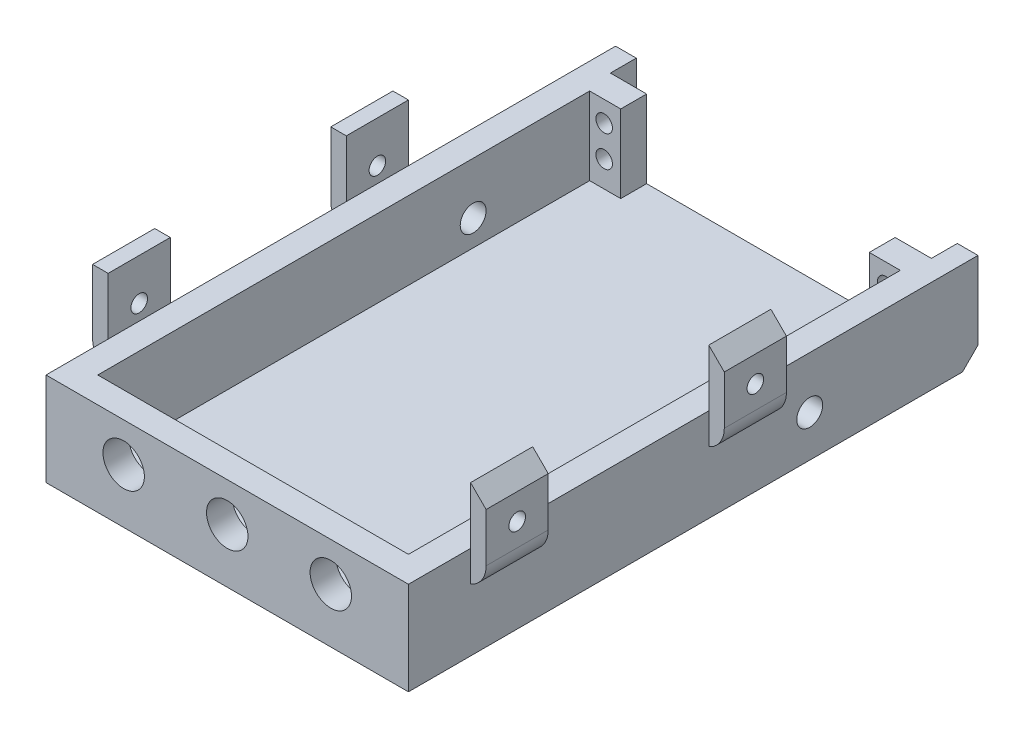
SolidWorks part; units mm, degrees
ref_plane "Alzado" through (0, 0, 0) normal (0, 0, 1) x (1, 0, 0)
ref_plane "Planta" through (0, 0, 0) normal (0, 1, 0) x (1, 0, 0)
ref_plane "Vista lateral" through (0, 0, 0) normal (1, 0, 0) x (0, 0, -1)
sketch "Croquis1" plane through (0, 0, 0) normal (0, 1, 0) x (1, 0, 0)
  line L1 (-35, 52.5) -> (35, 52.5)
  line L2 (-35, 52.5) -> (-35, -52.5)
  line L3 (-35, -52.5) -> (35, -52.5)
  line L4 (35, 52.5) -> (35, -52.5)
  line L5 (-35, 52.5) -> (35, -52.5) construction
  line L6 (-35, -52.5) -> (35, 52.5) construction
  point P0 (0, 0)
  dimension "D1" = 105
  dimension "D2" = 70
extrude "Saliente-Extruir1" add sketch "Croquis1" along normal blind 3
sketch "Croquis2" plane through (0, 3, 0) normal (0, 1, 0) x (1, 0, 0)
  line L1 (-35, 52.5) -> (-30, 52.5)
  line L2 (-35, 52.5) -> (-35, -52.5)
  line L4 (-30, 52.5) -> (-30, -47.5)
  line L5 (35, 52.5) -> (-35, 52.5) construction
  line L7 (35, -52.5) -> (35, 52.5)
  line L8 (35, 52.5) -> (30, 52.5)
  line L9 (30, -47.5) -> (30, 52.5)
  line L10 (-35, -52.5) -> (35, -52.5)
  line L12 (-30, -47.5) -> (30, -47.5)
  dimension "D1" = 5
  dimension "D2" = 5
  dimension "D3" = 100
  dimension "D4" = 100
extrude "Saliente-Extruir2" add sketch "Croquis2" along normal blind 15
ref_plane "Plano1" through (0, 0, -46.5) normal (0, 0, -1) x (-1, 0, 0)
sketch "Croquis10" plane through (35, 0, 0) normal (1, 0, 0) x (0, 0, -1)
  line L0 (11.5, 29) -> (11.5, 12) construction
  line L5 (-31.5, 18) -> (8.5, 18) construction
  line L10 (55, 0) -> (-55, 0) construction
  line L15 (8.5, 12) -> (17.5, 12)
  line L16 (8.5, 12) -> (8.5, 29)
  line L17 (8.5, 29) -> (17.5, 29)
  line L18 (17.5, 12) -> (17.5, 29)
  line L19 (-34.5, 12) -> (-28.5, 12)
  line L20 (11.5, 12) -> (5.5, 12)
  line L22 (11.5, 29) -> (5.5, 29)
  line L23 (5.5, 12) -> (5.5, 29)
  line L24 (-31.5, 12) -> (-40.5, 12)
  line L25 (-11.5, 11.4546) -> (-11.5, 24.5454)
  line L26 (52.5, 18) -> (52.5, 0) construction
  line L27 (-52.5, 18) -> (-52.5, 0) construction
  line L28 (-52.5, 0) -> (52.5, 0) construction
  line L29 (-40.5, 12) -> (-40.5, 29)
  line L30 (-34.5, 29) -> (-28.5, 29)
  line L31 (-31.5, 29) -> (-40.5, 29)
  line L32 (-28.5, 12) -> (-28.5, 29)
  circle A1 centre (11.5, 21) radius 1.6
  circle A2 centre (-34.5, 21) radius 1.6
  point P23 (8.5, 18)
  point P25 (-11.5, 18)
  point P26 (7.9335, 18)
  point P27 (0, 0)
  point P28 (8.5, 18)
  point P29 (7.535, 18)
  point P30 (0, 0)
  line M7 (52.5, 18) -> (-52.5, 18)
  dimension "D10" = 3.2
  dimension "D8" = 9
  dimension "D4" = 8
  dimension "D2" = 12
  dimension "D3" = 35
  dimension "D5" = 12
  dimension "D6" = 21
  dimension "D7" = 18
  dimension "D14" = 3
  dimension "D15" = 6
extrude "Saliente-Extruir4" add sketch "Croquis10" along normal blind 3 contours L18 L17 L16 A1 M7 | L15 L18 L16 M7 | L23 L20 L16 M7 | L23 L16 L22 M7 | L32 L30 L31 L29 A2 M7 | L19 L32 L29 L24 M7 region at (35, 15, -13) region at (35, 15, -7) region at (35, 15, 34.5) region at (35, 23.6622, 34.5) region at (35, 23.5, -7) region at (35, 23.7211, -13.1326)
fillet "Redondeo1" radius 5 2 edges at (38, 12, -11.5) (38, 12, 34.5)
mirror "Simetría1" about plane through (0, 0, 0) normal (1, 0, 0) of "Saliente-Extruir4", "Redondeo1"
sketch "Croquis12" plane through (-30, 0, 0) normal (1, 0, 0) x (0, 0, -1)
  line L0 (-47.5, 18) -> (52.5, 18) construction
  line L1 (47.5, 18) -> (52.5, 18)
  line L2 (47.5, 18) -> (47.5, 3)
  line L3 (47.5, 3) -> (52.5, 3)
  line L4 (52.5, 18) -> (52.5, 3)
  dimension "D1" = 5
extrude "Saliente-Extruir5" add sketch "Croquis12" along normal blind 6
mirror "Simetría2" about plane through (0, 0, 0) normal (1, 0, 0) of "Saliente-Extruir5"
sketch "Croquis13" plane through (0, 0, 52.5) normal (0, 0, 1) x (1, 0, 0)
  line L0 (-35, 0) -> (35, 0) construction
  line L2 (0, 10.5) -> (20, 10.5) construction
  line L3 (0, 10.5) -> (-20, 10.5) construction
  line L4 (0, 0) -> (0, 10.5) construction
  circle A0 centre (-20, 10.5) radius 4
  circle A1 centre (0, 10.5) radius 4
  circle A2 centre (20, 10.5) radius 4
  dimension "D1" = 8
  dimension "D2" = 8
  dimension "D3" = 8
  dimension "D4" = 10.5
  dimension "D5" = 20
  dimension "D6" = 20
extrude "Cortar-Extruir1" cut sketch "Croquis13" against normal up to next
sketch "Croquis14" plane through (0, 0, -52.5) normal (0, 0, -1) x (-1, 0, 0)
  line L0 (27.2, 14) -> (27.2, 8) construction
  line L2 (24, 18) -> (35, 18) construction
  line L3 (24, 3) -> (24, 18) construction
  circle A0 centre (27.2, 14) radius 1.6
  circle A1 centre (27.2, 8) radius 1.6
  dimension "D1" = 3.2
  dimension "D2" = 3.2
  dimension "D3" = 6
  dimension "D4" = 4
  dimension "D5" = 3.2
extrude "Cortar-Extruir2" cut sketch "Croquis14" against normal up to next
mirror "Simetría3" about plane through (0, 0, 0) normal (1, 0, 0) of "Cortar-Extruir2"
sketch "Croquis15" plane through (0, 0, -52.5) normal (0, 0, -1) x (-1, 0, 0)
  line L0 (-27.2, 14) -> (27.2, 14) construction
sketch "Croquis16" plane through (-35, 0, 0) normal (-1, 0, 0) x (0, 0, 1)
  line L0 (0, 0) -> (0, 8) construction
  line L1 (-52.5, 0) -> (52.5, 0) construction
  line L2 (0, 8) -> (-25, 8) construction
  circle A0 centre (-25, 8) radius 2.5
  dimension "D1" = 5
  dimension "D2" = 8
  dimension "D3" = 25
extrude "Cortar-Extruir3" cut sketch "Croquis16" against normal blind 70
sketch "Croquis17" plane through (0, 0, 0) normal (0, 1, 0) x (1, 0, 0)
  line L1 (35, 52.5) -> (31, 52.5)
  line L2 (35, 52.5) -> (35, 57.5)
  line L3 (35, 57.5) -> (31, 57.5)
  line L4 (31, 52.5) -> (31, 57.5)
extrude "Saliente-Extruir6" add sketch "Croquis17" along normal up to surface (18 mm away) up to face at (0, 18, -5.4)
mirror "Simetría4" about plane through (0, 0, 0) normal (1, 0, 0) of "Saliente-Extruir6"
chamfer "Chaflán1" distance 3 angle 45 2 edges at (-33, 0, -57.5) (33, 0, -57.5)
chamfer "Chaflán2" distance 3 angle 45 2 edges at (38, 29, -11.5) (38, 29, 34.5)
